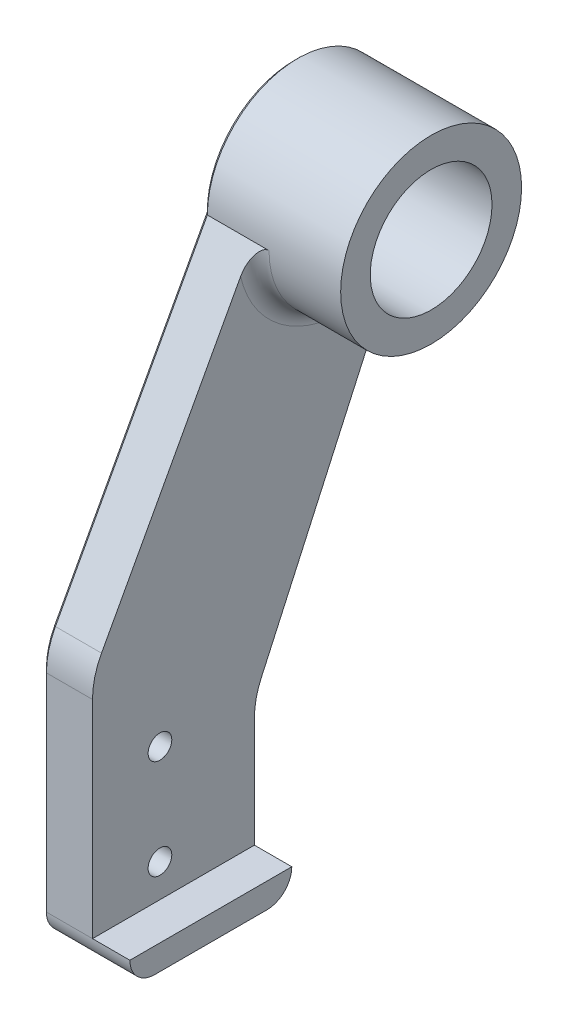
SolidWorks part; units mm, degrees
ref_plane "Front Plane" through (0, 0, 0) normal (0, 0, 1) x (1, 0, 0)
ref_plane "Top Plane" through (0, 0, 0) normal (0, 1, 0) x (1, 0, 0)
ref_plane "Right Plane" through (0, 0, 0) normal (1, 0, 0) x (0, 0, -1)
ref_plane "PX -15.420" through (-15.42, 0, 0) normal (1, 0, 0) x (0, 0, -1)
sketch "cheek sketch" plane through (-15.42, 0, 0) normal (1, 0, 0) x (0, 0, -1)
  line L0 (-4.37, -38) -> (-30.37, -38)
  line L1 (-30.37, -38) -> (-30.37, 2.3)
  line L2 (-30.37, 2.3) -> (-4.525, 50)
  line L3 (-4.525, 50) -> (24.525, 50)
  line L4 (24.525, 50) -> (-4.37, -13.7)
  line L5 (-4.37, -13.7) -> (-4.37, -38)
extrude "cheek" add sketch "cheek sketch" along normal mid plane 8
ref_plane "PX -8.420" through (-8.42, 0, 0) normal (1, 0, 0) x (0, 0, -1)
sketch "boss sketch" plane through (-8.42, 0, 0) normal (1, 0, 0) x (0, 0, -1)
  circle A0 centre (10, 50) radius 14.525
extrude "boss" add sketch "boss sketch" along normal mid plane 22
ref_plane "PX -8.670" through (-8.67, 0, 0) normal (1, 0, 0) x (0, 0, -1)
sketch "lip under the leg sketch" plane through (-8.67, 0, 0) normal (1, 0, 0) x (0, 0, -1)
  line L0 (-4.37, -38) -> (-4.37, -34)
  line L1 (-4.37, -34) -> (-30.37, -34)
  line L2 (-30.37, -34) -> (-30.37, -38)
  line L3 (-30.37, -38) -> (-4.37, -38)
extrude "lip under the leg" add sketch "lip under the leg sketch" along normal mid plane 6.5
ref_plane "PX -5.920" through (-5.92, 0, 0) normal (1, 0, 0) x (0, 0, -1)
sketch "socket sketch" plane through (-5.92, 0, 0) normal (1, 0, 0) x (0, 0, -1)
  circle A0 centre (10, 50) radius 9.775
extrude "socket" cut sketch "socket sketch" against normal mid plane 19
sketch "screw holes sketch" plane through (-15.42, 0, 0) normal (1, 0, 0) x (0, 0, -1)
  circle A0 centre (-19.54, -28.7) radius 1.9
  circle A1 centre (-19.54, -12.7) radius 1.9
extrude "screw holes" cut sketch "screw holes sketch" against normal mid plane 10
fillet "cheek corners" radius 4 2 edges at (-12.42, -38, 30.37) (-12.42, -38, 4.37) tangent propagation no
fillet "stem blend" radius 12 2 edges at (-15.42, -13.7, 4.37) (-15.42, 2.3, 30.37) tangent propagation no
fillet "boss root" radius 2.5 1 edges at (-11.42, 36.7723, -3.9998) tangent propagation no
chamfer "bed face chamfer" distance 0.6 angle 45 12 edges at (-19.42, -36.8284, 29.1984) (-19.42, -38, 17.37) (-19.42, -36.8284, 5.5416) (-19.42, -25.1472, 4.37) (-19.42, -13.7586, 4.099) (-19.42, 13.867, -8.1347) (-19.42, 63.2277, -16.0002) (-19.42, 27.4873, 16.7229) (-19.42, 2.2067, 30.0021) (-19.42, -17.371, 30.37) (-19.42, -12.7, 21.44) (-19.42, -28.7, 21.44)
equation "\"diffL\" = 608.8mm"
equation "\"diffW\" = 329.4mm"
equation "\"diffT\" = 2.9mm"
equation "\"chanSlotW\" = 12.9mm"
equation "\"chanSlotDepth\" = 11.13mm"
equation "\"chanFloor\" = 1.57mm"
equation "\"chanLeg\" = 12.7mm"
equation "\"lightL\" = 604.8mm"
equation "\"lightW\" = 330.2mm"
equation "\"lightH\" = 92mm"
equation "\"lightSideFlat\" = 30mm"
equation "\"lightSlopeLen\" = 38.9mm"
equation "\"lightWingDepth\" = 50.1mm"
equation "\"lightWingFlat\" = 90.2mm"
equation "\"lightChanW\" = 99.6mm"
equation "\"lightChanStand\" = 44.1mm"
equation "\"insFlangeD\" = 12.3mm"
equation "\"insFromEnd\" = 20.7mm"
equation "\"insUpSlope\" = 20.8mm"
equation "\"gaugeH\" = 10mm"
equation "\"gaugeStepLen\" = 14mm"
equation "\"gaugeStepW0\" = 13.1mm"
equation "\"gaugeStepDW\" = 0.2mm"
equation "\"gaugeSteps\" = 5mm"
equation "\"gaugeHandleLen\" = 30mm"
equation "\"gaugeHandleW\" = 24mm"
equation "\"gaugeSlot0\" = 3mm"
equation "\"gaugeSlotD\" = 0.1mm"
equation "\"gaugeSlotDepth\" = 8mm"
equation "\"gap\" = 25.4mm"
equation "\"edgeL\" = 1mm"
equation "\"edgeW\" = 0.75mm"
equation "\"proud\" = 2.5mm"
equation "\"seatClr\" = 0.15mm"
equation "\"tongueClrZ\" = 0.1mm"
equation "\"tongueClrX\" = 0.25mm"
equation "\"tongueLen\" = 30mm"
equation "\"armSide\" = 45mm"
equation "\"armEnd\" = 20mm"
equation "\"brkW\" = 26mm"
equation "\"brkT\" = 7mm"
equation "\"brkSeatClr\" = 0.3mm"
equation "\"brkScrewSpan\" = 16mm"
equation "\"pilotD\" = 4.3mm"
equation "\"pilotDepth\" = 8mm"
equation "\"screwClrD\" = 3.8mm"
equation "\"jogBelow\" = 4mm"
equation "\"padT\" = 7mm"
equation "\"padLen\" = 36mm"
equation "\"m6Clr\" = 9mm"
equation "\"m6Slot\" = 5mm"
equation "\"flangeRelD\" = 18mm"
equation "\"flangeRelDepth\" = 1.5mm"
equation "\"relLen\" = 5mm"
equation "\"relDepth\" = 3.3mm"
equation "\"knockN\" = 100mm"
equation "\"petgcfE\" = 3000mm"
equation "\"mockExtent\" = 110mm"
equation "\"relZnear\" = 9.4mm"
equation "\"relZfar\" = 23.4mm"
equation "\"headD\" = 8mm"
equation "\"headH\" = 2.5mm"
equation "\"headFromEnd\" = 6.8mm"
equation "\"headBack\" = 16.4mm"
equation "\"sideClr\" = 0.4mm"
equation "\"cornerRelR\" = 1.5mm"
equation "\"cornerRelBack\" = 0.6mm"
equation "\"endHeadH\" = 2.8mm"
equation "\"footClr\" = 1.2mm"
equation "\"footEndClr\" = 3.5mm"
equation "\"footBlockClr\" = 0.5mm"
equation "\"footBack\" = 85mm"
equation "\"footFwd\" = 10mm"
equation "\"footBraceEnd\" = 3mm"
equation "\"spacerLen\" = 60mm"
equation "\"spacerShort\" = 0.5mm"
equation "\"spacerCham\" = 0.8mm"
equation "\"spacerPerSide\" = 3mm"
equation "\"spacerPerEnd\" = 1mm"
equation "\"toolR\" = 9mm"
equation "\"visR\" = 4mm"
equation "\"edgeR\" = 1mm"
equation "\"bendOutR\" = 5mm"
equation "\"insideR\" = 2.5mm"
equation "\"footCornerR\" = 10mm"
equation "\"footFrontR\" = 8mm"
equation "\"braceKinkR\" = 12mm"
equation "\"bedCham\" = 1mm"
equation "\"bedChamSmall\" = 0.6mm"
equation "\"soleTopR\" = 2mm"
equation "\"cornerR\" = 6mm"
equation "\"rimInR\" = 1mm"
equation "\"insFlangeH\" = 1mm"
equation "\"insHoleFinishD\" = 4.5mm"
equation "\"insLen\" = 6.4mm"
equation "\"cgInset\" = 4mm"
equation "\"lampWeightN\" = 51mm"
equation "\"frameWeightN\" = 10mm"
equation "\"bumpIn\" = 8mm"
equation "\"bumpH\" = 3mm"
equation "\"legBelowFront\" = 2mm"
equation "\"lipClr\" = 0.1mm"
equation "\"revealR\" = 2mm"
equation "\"frontCham\" = 1mm"
equation "\"leanDeg\" = 5mm"
equation "\"footTailT\" = 6mm"
equation "\"v1LeanDeg\" = 4.5mm"
equation "\"toeNoseR\" = 5mm"
equation "\"petgE\" = 2000mm"
equation "\"cheekT\" = 8mm"
equation "\"handleUp\" = 50mm"
equation "\"handleZ\" = -10mm"
equation "\"gripD\" = 19.05mm"
equation "\"gripClr\" = 0.5mm"
equation "\"bossWall\" = 5mm"
equation "\"bossLen\" = 14mm"
equation "\"socketFloor\" = 4mm"
equation "\"barEndClr\" = 1mm"
equation "\"lipH\" = 4mm"
equation "\"lipDeep\" = 6mm"
